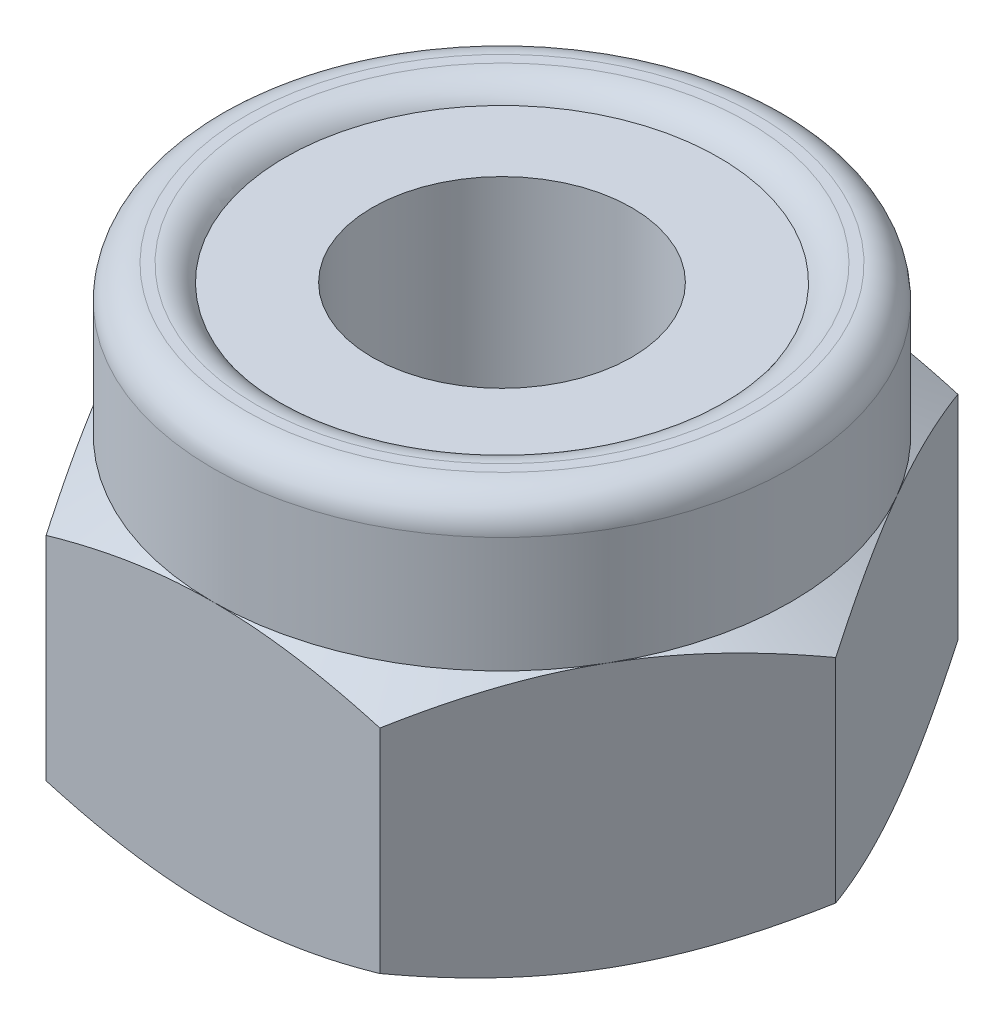
SolidWorks part; units mm, degrees
ref_plane "Front" through (0, 0, 0) normal (0, 0, 1) x (1, 0, 0)
ref_plane "Top" through (0, 0, 0) normal (0, 1, 0) x (1, 0, 0)
ref_plane "Right" through (0, 0, 0) normal (1, 0, 0) x (0, 0, -1)
sketch "Sketch1" plane through (0, 0, 0) normal (0, 1, 0) x (1, 0, 0)
  line L1 (4.0415, 0) -> (2.0207, 3.5)
  line L2 (2.0207, 3.5) -> (-2.0207, 3.5)
  line L3 (-2.0207, 3.5) -> (-4.0415, 0)
  line L4 (-4.0415, 0) -> (-2.0207, -3.5)
  line L5 (-2.0207, -3.5) -> (2.0207, -3.5)
  line L6 (2.0207, -3.5) -> (4.0415, 0)
  circle A0 centre (0, 0) radius 3.5 construction
extrude "Base-Extrude" add sketch "Sketch1" along normal blind 3.2
sketch "Sketch2" plane through (0, 3.2, 0) normal (0, 1, 0) x (-1, 0, 0)
  line L0 (2.0207, 3.5) -> (-2.0207, 3.5) construction
  circle A0 centre (0, 0) radius 3.5
extrude "Boss-Extrude1" add sketch "Sketch2" along normal blind 1.8
sketch "Sketch3" plane through (0, 5, 0) normal (0, 1, 0) x (-1, 0, 0)
  circle A0 centre (0, 0) radius 1.2565
  dimension "Nylon Dia" = 2.513
extrude "Cut-Extrude1" cut sketch "Sketch3" against normal blind 1.8
sketch "Sketch4" plane through (0, 5, 0) normal (0, 1, 0) x (-1, 0, 0)
  circle A0 centre (0, 0) radius 2.625
  dimension "D1" = 5.25
extrude "Cut-Extrude2" cut sketch "Sketch4" against normal blind 0.2
sketch "Sketch5" plane through (0, 4.8, 0) normal (0, 1, 0) x (-1, 0, 0)
  circle A0 centre (0, 0) radius 1.5706
  dimension "Thread Size" = 3.1412
extrude "Cut-Extrude3" cut sketch "Sketch5" against normal through all
fillet "Fillet3" radius 0.4 2 edges at (0, 5, 2.625) (0, 5, 3.5)
ref_plane "Plane1" through (0, 2.7, 0) normal (0, 1, 0) x (-1, 0, 0)
ref_plane "Plane2" through (0, 20, 0) normal (0, 1, 0) x (-1, 0, 0)
sketch "Sketch15" plane through (0, 0, 0) normal (0, 0, 1) x (1, 0, 0)
  line L0 (-3.5, 3.2) -> (-21.3981, -7.1335)
  line L2 (-3.5, 3.2) -> (-3.5, 11.2)
  line L3 (-3.5, 11.2) -> (-21.3981, -7.1335)
  line L6 (0, 0) -> (0, 46.027) construction
  line L7 (0, 4.6) -> (0, 3.2) construction
  dimension "D1" = 8
  dimension "D2" = 60
  dimension "Chamf Height" = 3.2
revolve "Cut-Revolve1" cut sketch "Sketch15" angle 360 about L6
sketch "Sketch16" plane through (0, 0, 0) normal (0, 0, 1) x (1, 0, 0)
  line L0 (-5.1204, 0) -> (4.9698, 0) construction
  line L1 (-3.5, 0) -> (-109.5649, 61.2366)
  line L2 (-109.5649, 61.2366) -> (-3.5, -23.6378)
  line L3 (-3.5, -23.6378) -> (-3.5, 0)
  line L4 (0, 0) -> (0, 4.8781) construction
  line L5 (0, 4.6) -> (0, 3.2) construction
  dimension "D1" = 30
  dimension "D2" = 7
revolve "Cut-Revolve2" cut sketch "Sketch16" angle 360 about L4
